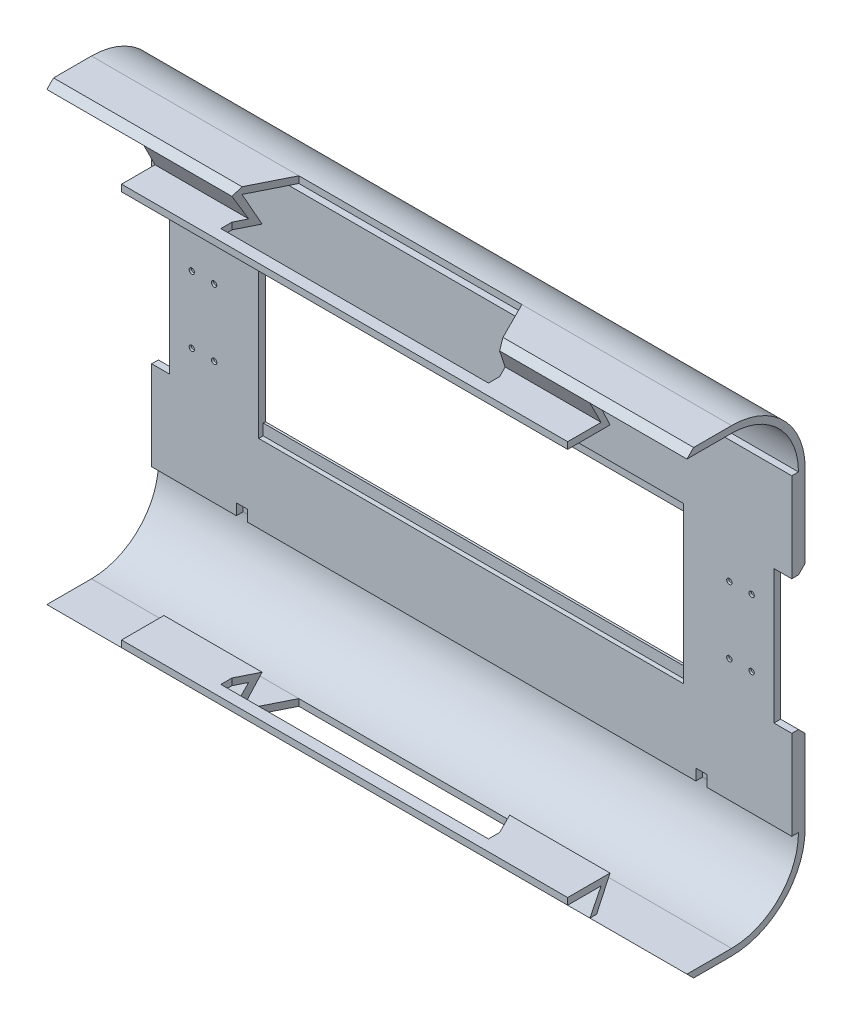
SolidWorks part; units mm, degrees
ref_plane "前视基准面" through (0, 0, 0) normal (0, 0, 1) x (1, 0, 0)
ref_plane "上视基准面" through (0, 0, 0) normal (0, 1, 0) x (1, 0, 0)
ref_plane "右视基准面" through (0, 0, 0) normal (1, 0, 0) x (0, 0, -1)
sketch "草图1" plane through (0, 0, 0) normal (0, 0, 1) x (1, 0, 0)
  line L61 (-143.25, 30) -> (-143.25, 70)
  line L65 (-135.25, 30) -> (-143.25, 30)
  line L80 (-105.25, 65) -> (-105.25, 70)
  line L81 (-143.25, 70) -> (-105.25, 70)
  line L109 (-105.25, 65) -> (-100.25, 65)
  line L110 (-100.25, 65) -> (-100.25, 70)
  line L112 (-100.25, 70) -> (100.75, 70)
  line L115 (-135.25, -30) -> (-135.25, 30)
  line L116 (135.75, -30) -> (135.75, 30)
  line L117 (100.75, 65) -> (100.75, 70)
  line L118 (105.75, 65) -> (100.75, 65)
  line L119 (143.75, 70) -> (105.75, 70)
  line L120 (105.75, 65) -> (105.75, 70)
  line L121 (135.75, 30) -> (143.75, 30)
  line L122 (143.75, 30) -> (143.75, 70)
  line L123 (143.75, -30) -> (143.75, -70)
  line L124 (135.75, -30) -> (143.75, -30)
  line L125 (105.75, -65) -> (105.75, -70)
  line L126 (143.75, -70) -> (105.75, -70)
  line L127 (105.75, -65) -> (100.75, -65)
  line L128 (100.75, -65) -> (100.75, -70)
  line L129 (-100.25, -70) -> (100.75, -70)
  line L130 (-100.25, -65) -> (-100.25, -70)
  line L131 (-105.25, -65) -> (-100.25, -65)
  line L132 (-143.25, -70) -> (-105.25, -70)
  line L133 (-105.25, -65) -> (-105.25, -70)
  line L134 (-135.25, -30) -> (-143.25, -30)
  line L135 (-143.25, -30) -> (-143.25, -70)
  point P23 (135.75, 0)
extrude "凸台-拉伸1" add sketch "草图1" along normal blind 3
ref_plane "基准面1" through (-143.25, 0, 0) normal (-1, 0, 0) x (0, 0, 1)
sketch "草图2" plane through (-143.25, 0, 0) normal (-1, 0, 0) x (0, 0, 1)
  line L1 (0, 70) -> (0, 30)
  line L2 (0, 30) -> (-3, 33)
  line L3 (-3, 33) -> (-3, 70)
  line L4 (50, 100) -> (47, 103)
  line L8 (30, 103) -> (47, 103)
  line L17 (45, 90) -> (50, 100)
  line L18 (45, 90) -> (60, 90)
  line L19 (60, 90) -> (60, 87)
  line L20 (60, 87) -> (41, 87)
  line L21 (41, 87) -> (47, 100)
  line L22 (30, 100) -> (47, 100)
  line L24 (30, -100) -> (47, -100)
  line L25 (41, -87) -> (47, -100)
  line L26 (60, -87) -> (41, -87)
  line L27 (60, -90) -> (60, -87)
  line L28 (45, -90) -> (60, -90)
  line L29 (45, -90) -> (50, -100)
  line L30 (30, -103) -> (47, -103)
  line L31 (50, -100) -> (47, -103)
  line L32 (-3, -33) -> (-3, -70)
  line L33 (0, -30) -> (-3, -33)
  line L34 (0, -70) -> (0, -30)
  arc A0 (0, 70) -> (30, 100) centre (30, 70) cw
  arc A1 (-3, 70) -> (30, 103) centre (30, 70) cw
  arc A4 (-3, -70) -> (30, -103) centre (30, -70) ccw
  arc A5 (0, -70) -> (30, -100) centre (30, -70) ccw
extrude "凸台-拉伸2" add sketch "草图2" against normal blind 287
sketch "草图4" plane through (-143.25, 0, 0) normal (-1, 0, 0) x (0, 0, 1)
  line L1 (30, 100) -> (47, 100) construction
  line L4 (60.2366, -100) -> (38.5, -100)
  line L5 (60.2366, -100) -> (60.2366, 100)
  line L6 (60.2366, 100) -> (38.5, 100)
  line L7 (38.5, -100) -> (38.5, 100)
extrude "切除-拉伸1" cut sketch "草图4" against normal blind 43.5
ref_plane "基准面2" through (143.75, 0, 0) normal (1, 0, 0) x (0, 0, -1)
sketch "草图5" plane through (143.75, 0, 0) normal (1, 0, 0) x (0, 0, -1)
  line L1 (-30, 100) -> (-47, 100) construction
  line L4 (-63.1672, -100) -> (-39.752, -100)
  line L5 (-63.1672, -100) -> (-63.1672, 100)
  line L6 (-63.1672, 100) -> (-39.752, 100)
  line L7 (-39.752, -100) -> (-39.752, 100)
extrude "切除-拉伸2" cut sketch "草图5" against normal blind 43.5
ref_plane "基准面3" through (0, 103, 0) normal (0, 1, 0) x (1, 0, 0)
sketch "草图6" plane through (0, 103, 0) normal (0, 1, 0) x (1, 0, 0)
  line L1 (143.75, -30) -> (-143.25, -30) construction
  line L2 (100.25, -50) -> (-99.75, -50) construction
  line L3 (0.25, -30) -> (-50.25, -30)
  line L4 (0.25, -30) -> (49.75, -30)
  line L7 (-50.25, -30) -> (-60.25, -50)
  line L8 (-60.25, -50) -> (-60.25, -55)
  line L9 (-60.25, -55) -> (59.75, -55)
  line L10 (59.75, -55) -> (59.75, -50)
  line L11 (59.75, -50) -> (49.75, -30)
extrude "切除-拉伸3" cut sketch "草图6" against normal through all
hole_wizard "大小六角凹头盖螺钉柱孔1" positions "3D草图3" profile "草图9" counterbore size "M2" standard "AS" end condition through all
sketch3d "3D草图3"
  line L0 (135.75, 0, 0) -> (125.75, 0, 0)
  line L1 (135.75, -30, 0) -> (135.75, 30, 0) construction
  line L3 (125.75, 0, 0) -> (125.75, 15, 0)
  line L5 (125.75, 0, 0) -> (125.75, -15, 0)
  point P15 (125.75, -15, 0)
  point P17 (125.75, 15, 0)
  point P26 (-125.25, -15, 0)
  point P31 (-125.25, 15, 0)
  point P39 (-115.25, -15, 0)
  point P44 (-115.25, 15, 0)
  point P48 (115.75, -15, 0)
  point P50 (115.75, 15, 0)
sketch "草图9" plane through (115.75, 15, 0) normal (1, 0, 0) x (0, 1, 0)
  line L0 (0, 0) -> (0, 60)
  line L1 (0, 60) -> (1.2, 60)
  line L3 (1.2, 60) -> (1.2, 2)
  line L4 (2.15, 2) -> (1.2, 2)
  line L5 (2.15, 2) -> (2.15, 0.0241)
  line L6 (2.15, 0.0241) -> (2.175, 0)
  line L7 (2.175, 0) -> (0, 0)
  line L8 (-2.15, 0.0241) -> (-2.175, 0) construction
  line L11 (0, -6.35) -> (0, 107.95) construction
  dimension "通孔孔直径" = 2.4
  dimension "通孔孔深度" = 60
  dimension "柱形沉头孔直径" = 4.3
  dimension "柱形沉头孔深度" = 2
  dimension "近端锥形沉头孔直径" = 4.35
  dimension "近端锥形沉头孔角度" = 92
ref_plane "基准面5" through (0, 0, 3) normal (0, 0, 1) x (1, 0, 0)
sketch "草图10" plane through (0, 0, 3) normal (0, 0, 1) x (1, 0, 0)
  line L0 (-95.25, -35) -> (-95.25, 35)
  line L2 (-95.25, -35) -> (95.25, -35)
  line L4 (-95.25, 35) -> (95.25, 35)
  line L5 (95.25, -35) -> (95.25, 35)
  point P8 (0, 35)
extrude "切除-拉伸4" cut sketch "草图10" against normal blind 2
sketch "草图11" plane through (0, 0, 0) normal (0, 0, 1) x (1, 0, 0)
  line L0 (-95.25, 30) -> (-95.25, -30)
  line L1 (-95.25, 35) -> (-95.25, -35) construction
  line L2 (-95.25, 30) -> (95.25, 30)
  line L5 (95.25, 30) -> (95.25, -30)
  line L6 (-95.25, -30) -> (95.25, -30)
  point P10 (95.25, 0)
extrude "切除-拉伸5" cut sketch "草图11" along normal blind 1
